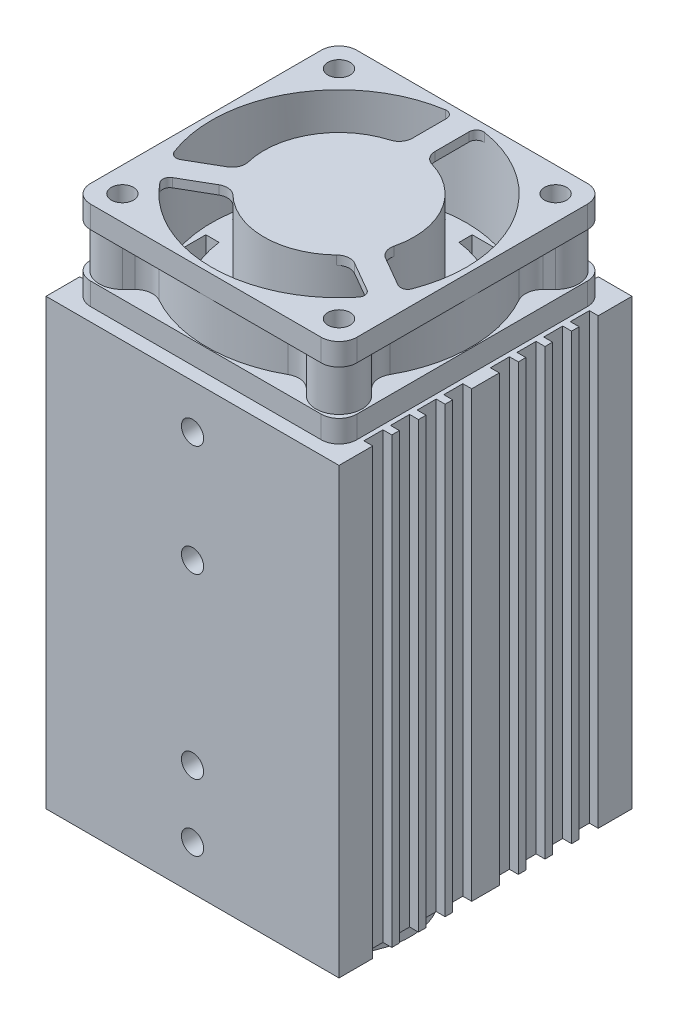
SolidWorks part; units mm, degrees
ref_plane "Ebene vorne" through (0, 0, 0) normal (0, 0, 1) x (1, 0, 0)
ref_plane "Ebene oben" through (0, 0, 0) normal (0, 1, 0) x (1, 0, 0)
ref_plane "Ebene rechts" through (0, 0, 0) normal (1, 0, 0) x (0, 0, -1)
sketch "Skizze1" plane through (0, 0, 0) normal (0, 1, 0) x (1, 0, 0)
  line L1 (-16.5, -16.5) -> (16.5, -16.5)
  line L2 (-16.5, -16.5) -> (-16.5, 16.5)
  line L3 (-16.5, 16.5) -> (16.5, 16.5)
  line L4 (16.5, -16.5) -> (16.5, 16.5)
  line L5 (-16.5, -16.5) -> (16.5, 16.5) construction
  line L6 (-16.5, 16.5) -> (16.5, -16.5) construction
  point P0 (0, 0)
  dimension "D1" = 33
extrude "Aufsatz-Linear austragen1" add sketch "Skizze1" along normal blind 50
sketch "Skizze2" plane through (0, 0, 16.5) normal (0, 0, 1) x (1, 0, 0)
  circle A0 centre (0, 5) radius 1.25
  circle A1 centre (0, 45) radius 1.25
  circle A2 centre (0, 12.5) radius 1.25
  circle A3 centre (0, 32.5) radius 1.25
  dimension "D1" = 2.5
  dimension "D2" = 5
  dimension "D4" = 7.5
  dimension "D5" = 27.5
extrude "Schnitt-Linear austragen1" cut sketch "Skizze2" against normal blind 5
sketch "Skizze16" plane through (0, 0, 0) normal (0, 0, 1) x (1, 0, 0)
  line L0 (0, 0) -> (0, -8.5) construction
  line L1 (-2.45, 0) -> (-2.45, -8.5)
  line L2 (-16.5, 0) -> (16.5, 0) construction
  line L3 (-2.45, -8.5) -> (-8, -8.5)
  line L4 (-8, -8.5) -> (-8, -3.5)
  line L5 (-8, -3.5) -> (-4.5, -3.5)
  line L6 (-4.5, -3.5) -> (-4.5, 0)
  line L7 (-4.5, 0) -> (-2.45, 0)
  dimension "D1" = 4.9
  dimension "D2" = 16
  dimension "D3" = 8.5
  dimension "D4" = 5
  dimension "D5" = 9
revolve "Rotation1" add sketch "Skizze16" angle 360 about L0
sketch "Skizze7" plane through (0, 50, 0) normal (0, 1, 0) x (1, 0, 0)
  line L0 (-16.5, 16.5) -> (0, 0) construction
  line L1 (0, 0) -> (0, 16.5) construction
  line L2 (16.5, 16.5) -> (-16.5, 16.5) construction
  line L3 (-1.5, 12.0067) -> (-1.5, 13.5)
  line L4 (0, 0) -> (-16.5, 0) construction
  line L5 (-16.5, 16.5) -> (-16.5, -16.5) construction
  line L6 (-13.5, 1.5) -> (-12.0067, 1.5)
  line L7 (-12.1976, 11.1976) -> (-12.1976, 10.4476)
  line L8 (-11.1976, 12.1976) -> (-10.4476, 12.1976)
  line L9 (-1.5, 13.5) -> (-11.0287, 13.5)
  line L10 (-13.5, 1.5) -> (-13.5, 11.0287)
  line L11 (1.5, 13.5) -> (1.5, 12.0067)
  line L12 (12.0067, 1.5) -> (13.5, 1.5)
  line L13 (13.5, 1.5) -> (13.5, 11.0287)
  line L14 (12.1976, 11.1976) -> (12.1976, 10.4476)
  line L15 (11.1976, 12.1976) -> (10.4476, 12.1976)
  line L16 (1.5, 13.5) -> (11.0287, 13.5)
  line L17 (13.5, -1.5) -> (12.0067, -1.5)
  line L18 (1.5, -12.0067) -> (1.5, -13.5)
  line L19 (0, 0) -> (0, 16.5) construction
  line L20 (1.5, -13.5) -> (11.0287, -13.5)
  line L21 (11.1976, -12.1976) -> (10.4476, -12.1976)
  line L22 (12.1976, -11.1976) -> (12.1976, -10.4476)
  line L23 (13.5, -1.5) -> (13.5, -11.0287)
  line L24 (-1.5, -13.5) -> (-1.5, -12.0067)
  line L25 (-12.0067, -1.5) -> (-13.5, -1.5)
  line L26 (-13.5, -1.5) -> (-13.5, -11.0287)
  line L27 (-12.1976, -11.1976) -> (-12.1976, -10.4476)
  line L28 (-11.1976, -12.1976) -> (-10.4476, -12.1976)
  line L29 (-1.5, -13.5) -> (-11.0287, -13.5)
  line L36 (0, 0) -> (-16.5, 0) construction
  line L38 (12.0067, 1.5) -> (13.5, 1.5) [skipped]
  line L39 (1.5, 13.5) -> (1.5, 12.0067) [skipped]
  line L40 (11.1976, 12.1976) -> (10.4476, 12.1976) [skipped]
  line L41 (12.1976, 11.1976) -> (12.1976, 10.4476) [skipped]
  line L42 (13.5, 1.5) -> (13.5, 11.0287) [skipped]
  line L43 (1.5, 13.5) -> (11.0287, 13.5) [skipped]
  line L44 (1.5, -12.0067) -> (1.5, -13.5) [skipped]
  line L45 (13.5, -1.5) -> (12.0067, -1.5) [skipped]
  line L46 (12.1976, -11.1976) -> (12.1976, -10.4476) [skipped]
  line L47 (11.1976, -12.1976) -> (10.4476, -12.1976) [skipped]
  line L48 (1.5, -13.5) -> (11.0287, -13.5) [skipped]
  line L49 (13.5, -1.5) -> (13.5, -11.0287) [skipped]
  line L50 (-12.0067, -1.5) -> (-13.5, -1.5) [skipped]
  line L51 (-1.5, -13.5) -> (-1.5, -12.0067) [skipped]
  line L52 (-11.1976, -12.1976) -> (-10.4476, -12.1976) [skipped]
  line L53 (-12.1976, -11.1976) -> (-12.1976, -10.4476) [skipped]
  line L54 (-13.5, -1.5) -> (-13.5, -11.0287) [skipped]
  line L55 (-1.5, -13.5) -> (-11.0287, -13.5) [skipped]
  line L56 (-16.5, -16.5) -> (0, 0) construction
  line L57 (0, 0) -> (0, -16.5) construction
  line L58 (16.5, -16.5) -> (0, 0) construction
  line L59 (0, 0) -> (0, -16.5) construction
  line L60 (0, 0) -> (16.5, 0) construction
  line L61 (0, 0) -> (16.5, 0) construction
  line L62 (16.5, 16.5) -> (0, 0) construction
  arc A0 (-11.1976, 12.1976) -> (-12.1976, 11.1976) centre (-12.1976, 12.1976) ccw
  arc A1 (-10.4476, 12.1976) -> (-11.0287, 13.5) centre (-12.1976, 12.1976) ccw
  arc A2 (-1.5, 12.0067) -> (-12.0067, 1.5) centre (0, 0) ccw
  arc A3 (-13.5, 11.0287) -> (-12.1976, 10.4476) centre (-12.1976, 12.1976) ccw
  arc A4 (12.0067, 1.5) -> (1.5, 12.0067) centre (0, 0) ccw
  arc A5 (12.1976, 10.4476) -> (13.5, 11.0287) centre (12.1976, 12.1976) ccw
  arc A6 (12.1976, 11.1976) -> (11.1976, 12.1976) centre (12.1976, 12.1976) ccw
  arc A7 (11.0287, 13.5) -> (10.4476, 12.1976) centre (12.1976, 12.1976) ccw
  arc A8 (1.5, -12.0067) -> (12.0067, -1.5) centre (0, 0) ccw
  arc A9 (10.4476, -12.1976) -> (11.0287, -13.5) centre (12.1976, -12.1976) ccw
  arc A10 (11.1976, -12.1976) -> (12.1976, -11.1976) centre (12.1976, -12.1976) ccw
  arc A11 (13.5, -11.0287) -> (12.1976, -10.4476) centre (12.1976, -12.1976) ccw
  arc A12 (-12.0067, -1.5) -> (-1.5, -12.0067) centre (0, 0) ccw
  arc A13 (-12.1976, -10.4476) -> (-13.5, -11.0287) centre (-12.1976, -12.1976) ccw
  arc A14 (-12.1976, -11.1976) -> (-11.1976, -12.1976) centre (-12.1976, -12.1976) ccw
  arc A15 (-11.0287, -13.5) -> (-10.4476, -12.1976) centre (-12.1976, -12.1976) ccw
  arc A16 (12.1976, 11.1976) -> (11.1976, 12.1976) centre (12.1976, 12.1976) ccw [skipped]
  arc A17 (12.1976, 10.4476) -> (13.5, 11.0287) centre (12.1976, 12.1976) ccw [skipped]
  arc A18 (12.0067, 1.5) -> (1.5, 12.0067) centre (0, 0) ccw [skipped]
  arc A19 (11.0287, 13.5) -> (10.4476, 12.1976) centre (12.1976, 12.1976) ccw [skipped]
  arc A20 (11.1976, -12.1976) -> (12.1976, -11.1976) centre (12.1976, -12.1976) ccw [skipped]
  arc A21 (10.4476, -12.1976) -> (11.0287, -13.5) centre (12.1976, -12.1976) ccw [skipped]
  arc A22 (1.5, -12.0067) -> (12.0067, -1.5) centre (0, 0) ccw [skipped]
  arc A23 (13.5, -11.0287) -> (12.1976, -10.4476) centre (12.1976, -12.1976) ccw [skipped]
  arc A24 (-12.1976, -11.1976) -> (-11.1976, -12.1976) centre (-12.1976, -12.1976) ccw [skipped]
  arc A25 (-12.1976, -10.4476) -> (-13.5, -11.0287) centre (-12.1976, -12.1976) ccw [skipped]
  arc A26 (-12.0067, -1.5) -> (-1.5, -12.0067) centre (0, 0) ccw [skipped]
  arc A27 (-11.0287, -13.5) -> (-10.4476, -12.1976) centre (-12.1976, -12.1976) ccw [skipped]
  point P59 (0, 0)
  point P66 (0, 0)
  dimension "D1" = 24.2
  dimension "D6" = 2
  dimension "D7" = 3.5
  dimension "D2" = 1.5
  dimension "D3" = 3
  dimension "D4" = 1.5
  dimension "D5" = 3
  dimension "D8" = 17.25
  dimension "D9" = 4
extrude "Schnitt-Linear austragen3" cut sketch "Skizze7" against normal up to surface (50 mm away) up to face at (0, 0, -4.5)
sketch "Skizze8" plane through (0, 50, 0) normal (0, 1, 0) x (1, 0, 0)
  line L0 (-16.5, 16.5) -> (-16.5, -16.5) construction
  line L1 (-16.5, 1.55) -> (-15.5, 1.55)
  line L2 (-16.5, 1.55) -> (-16.5, 3.7)
  line L3 (-16.5, 3.7) -> (-15.5, 3.7)
  line L4 (-15.5, 1.55) -> (-15.5, 3.7)
  line L5 (-15.5, 10.55) -> (-15.5, 9.7) construction
  line L6 (-16.5, 4.55) -> (-15.5, 4.55)
  line L7 (-16.5, 4.55) -> (-16.5, 6.7)
  line L8 (-16.5, 6.7) -> (-15.5, 6.7)
  line L9 (-15.5, 4.55) -> (-15.5, 6.7)
  line L10 (-16.5, 7.55) -> (-15.5, 7.55)
  line L11 (-16.5, 7.55) -> (-16.5, 9.7)
  line L12 (-16.5, 9.7) -> (-15.5, 9.7)
  line L13 (-15.5, 7.55) -> (-15.5, 9.7)
  line L14 (-16.5, 10.55) -> (-15.5, 10.55)
  line L15 (-16.5, 10.55) -> (-16.5, 12.7)
  line L16 (-16.5, 12.7) -> (-15.5, 12.7)
  line L17 (-15.5, 10.55) -> (-15.5, 12.7)
  line L18 (-15.5, 7.55) -> (-15.5, 6.7) construction
  line L19 (-15.5, 4.55) -> (-15.5, 3.7) construction
  line L20 (-16.5, 0) -> (0, 0) construction
  line L21 (-15.5, -3.7) -> (-15.5, -4.55) construction
  line L22 (-16.5, -1.55) -> (-15.5, -1.55)
  line L23 (-16.5, -1.55) -> (-16.5, -3.7)
  line L24 (-16.5, -3.7) -> (-15.5, -3.7)
  line L25 (-15.5, -1.55) -> (-15.5, -3.7)
  line L26 (-16.5, -4.55) -> (-15.5, -4.55)
  line L27 (-16.5, -4.55) -> (-16.5, -6.7)
  line L28 (-16.5, -6.7) -> (-15.5, -6.7)
  line L29 (-15.5, -4.55) -> (-15.5, -6.7)
  line L30 (-16.5, -7.55) -> (-15.5, -7.55)
  line L31 (-16.5, -7.55) -> (-16.5, -9.7)
  line L32 (-16.5, -9.7) -> (-15.5, -9.7)
  line L33 (-15.5, -7.55) -> (-15.5, -9.7)
  line L34 (-16.5, -10.55) -> (-15.5, -10.55)
  line L35 (-16.5, -10.55) -> (-16.5, -12.7)
  line L36 (-16.5, -12.7) -> (-15.5, -12.7)
  line L37 (-15.5, -10.55) -> (-15.5, -12.7)
  line L38 (-15.5, -6.7) -> (-15.5, -7.55) construction
  line L39 (-15.5, -9.7) -> (-15.5, -10.55) construction
  dimension "D1" = 2.15
  dimension "D2" = 0.85
  dimension "D3" = 3.1
  dimension "D4" = 1
extrude "Schnitt-Linear austragen4" cut sketch "Skizze8" against normal through all
pattern_circular "Kreismuster10" count 3 every 90 about axis through (0, -16.9706, 0) along (0, 1, 0) of "Schnitt-Linear austragen4" reverse direction yes
sketch "Skizze9" plane through (0, 50, 0) normal (0, 1, 0) x (1, 0, 0)
  line L1 (15, -15) -> (-15, -15)
  line L2 (15, -15) -> (15, 15)
  line L3 (15, 15) -> (-15, 15)
  line L4 (-15, -15) -> (-15, 15)
  line L5 (15, -15) -> (-15, 15) construction
  line L6 (15, 15) -> (-15, -15) construction
  point P0 (0, 0)
  dimension "D1" = 30
extrude "Aufsatz-Linear austragen4" add sketch "Skizze9" along normal blind 10 separate body
sketch "Skizze11" plane through (0, 60, 0) normal (0, 1, 0) x (1, 0, 0)
  line L0 (0, 15) -> (0, 0) construction
  line L1 (0, 0) -> (-12.4275, -7.175) construction
  line L2 (0, 0) -> (12.4275, -7.175) construction
  line L3 (-13.0179, -6.0379) -> (-7.8735, -3.0677)
  line L4 (-11.7379, -8.2549) -> (-6.5935, -5.2848)
  line L5 (6.5935, -5.2848) -> (11.7379, -8.2549)
  line L6 (7.8735, -3.0677) -> (13.0179, -6.0379)
  line L7 (-1.28, 14.2928) -> (-1.28, 8.3525)
  line L8 (1.28, 14.2928) -> (1.28, 8.3525)
  line L9 (-10.4457, -4.5528) -> (-9.1657, -6.7698) construction
  line L10 (10.4457, -4.5528) -> (9.1657, -6.7698) construction
  line L11 (-1.28, 11.3226) -> (1.28, 11.3226) construction
  line L12 (15, 15) -> (-15, 15) construction
  arc A0 (-1.28, 8.3525) -> (-7.8735, -3.0677) centre (0, 0) ccw
  arc A1 (-1.28, 14.2928) -> (-13.0179, -6.0379) centre (0, 0) ccw
  arc A2 (-6.5935, -5.2848) -> (6.5935, -5.2848) centre (0, 0) ccw
  arc A3 (-11.7379, -8.2549) -> (11.7379, -8.2549) centre (0, 0) ccw
  arc A4 (7.8735, -3.0677) -> (1.28, 8.3525) centre (0, 0) ccw
  arc A5 (13.0179, -6.0379) -> (1.28, 14.2928) centre (0, 0) ccw
  dimension "D1" = 16.9
  dimension "D2" = 28.7
  dimension "D3" = 120
  dimension "D4" = 2.56
extrude "Schnitt-Linear austragen5" cut sketch "Skizze11" against normal up to surface (10 mm away) up to face at (0, 50, 0)
sketch "Skizze12" plane through (0, 50, 0) normal (0, -1, 0) x (1, 0, 0)
  circle A0 centre (0, 0) radius 8.45
  circle A1 centre (0, 0) radius 14.35
extrude "Schnitt-Linear austragen6" cut sketch "Skizze12" against normal offset from surface (9 mm away) 1 up to face at (7.8678, 60, -4.5425)
sketch "Skizze13" plane through (0, 60, 0) normal (0, 1, 0) x (1, 0, 0)
  line L1 (12.1976, -12.1976) -> (-12.1976, -12.1976) construction
  line L2 (12.1976, -12.1976) -> (12.1976, 12.1976) construction
  line L3 (12.1976, 12.1976) -> (-12.1976, 12.1976) construction
  line L4 (-12.1976, -12.1976) -> (-12.1976, 12.1976) construction
  line L5 (12.1976, -12.1976) -> (-12.1976, 12.1976) construction
  line L6 (12.1976, 12.1976) -> (-12.1976, -12.1976) construction
  circle A0 centre (-12.1976, -12.1976) radius 1.25
  circle A1 centre (12.1976, -12.1976) radius 1.25
  circle A2 centre (-12.1976, 12.1976) radius 1.25
  circle A3 centre (12.1976, 12.1976) radius 1.25
  point P0 (0, 0)
  dimension "D2" = 2.5
  dimension "D1" = 34.5
extrude "Schnitt-Linear austragen7" cut sketch "Skizze13" against normal up to surface (10 mm away) up to face at (0, 50, 14.35)
fillet "Verrundung3" radius 2 4 edges at (-15, 55, 15) (-15, 55, -15) (15, 55, -15) (15, 55, 15)
fillet "Verrundung4" radius 0.8 6 edges at (-13.0179, 59.5, 6.0379) (-11.7379, 59.5, 8.2549) (-1.28, 59.5, -14.2928) (1.28, 59.5, -14.2928) (13.0179, 59.5, 6.0379) (11.7379, 59.5, 8.2549)
fillet "Verrundung5" radius 1.5 6 edges at (7.8735, 59.5, 3.0677) (6.5935, 59.5, 5.2848) (-6.5935, 59.5, 5.2848) (-7.8735, 59.5, 3.0677) (-1.28, 59.5, -8.3525) (1.28, 59.5, -8.3525)
ref_plane "Ebene1" through (0, 57.5, 0) normal (0, 1, 0) x (1, 0, 0)
sketch "Skizze14" plane through (0, 57.5, 0) normal (0, 1, 0) x (1, 0, 0)
  line L0 (-14.4142, 14.4142) -> (0, 0) construction
  line L1 (-15, 0) -> (0, 0) construction
  line L2 (-15, 13) -> (-15, -13) construction
  line L3 (-14.4142, -14.4142) -> (0, 0) construction
  line L4 (-13.3374, 9.6604) -> (-14.0361, 10.3591)
  line L5 (-15, 13) -> (-15, -13)
  line L6 (-14.0361, -10.3591) -> (-13.3374, -9.6604)
  line L7 (-14.4142, 14.4142) -> (-14.0361, 14.0361)
  line L8 (-14.0361, -14.0361) -> (-14.4142, -14.4142)
  arc A0 (-13, 15) -> (-15, 13) centre (-13, 13) ccw construction
  arc A1 (-15, -13) -> (-13, -15) centre (-13, -13) ccw construction
  arc A2 (-13.0059, 7.2703) -> (-13.0059, -7.2703) centre (0, 0) ccw
  arc A3 (-13.0059, -7.2703) -> (-13.3374, -9.6604) centre (-14.7516, -8.2462) cw
  arc A4 (-13.0059, 7.2703) -> (-13.3374, 9.6604) centre (-14.7516, 8.2462) ccw
  arc A5 (-14.0361, 14.0361) -> (-14.0361, 10.3591) centre (-12.1976, 12.1976) ccw
  arc A6 (-14.4142, 14.4142) -> (-15, 13) centre (-13, 13) ccw
  arc A7 (-14.0361, -10.3591) -> (-14.0361, -14.0361) centre (-12.1976, -12.1976) ccw
  arc A8 (-15, -13) -> (-14.4142, -14.4142) centre (-13, -13) ccw
  point P19 (-12.2127, -8.5358)
  point P22 (-12.2127, 8.5358)
  dimension "D1" = 14.9
  dimension "D3" = 2
  dimension "D2" = 2.6
extrude "Schnitt-Linear austragen8" cut sketch "Skizze14" against normal blind 5
pattern_circular "Kreismuster11" count 4 over 360 about axis through (0, -16.9706, 0) along (0, 1, 0) of "Schnitt-Linear austragen8"
